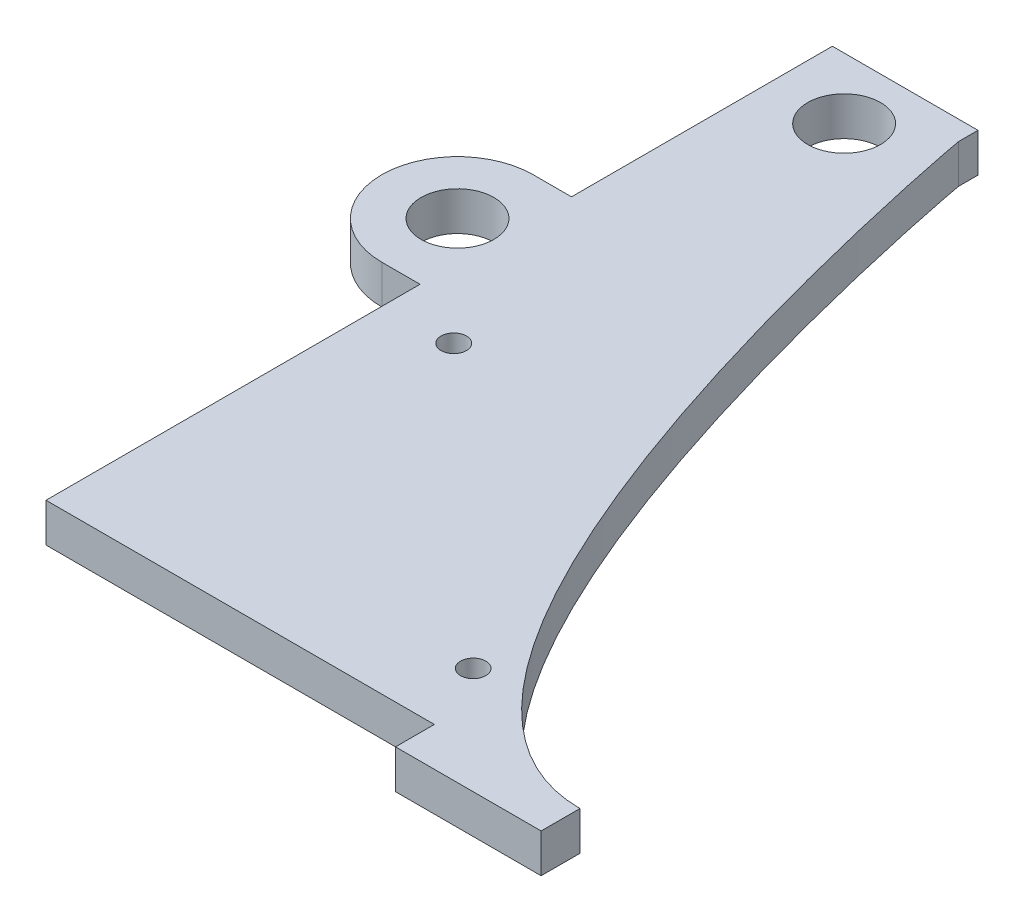
SolidWorks part; units mm, degrees
ref_plane "Front Plane" through (0, 0, 0) normal (0, 0, 1) x (1, 0, 0)
ref_plane "Top Plane" through (0, 0, 0) normal (0, 1, 0) x (1, 0, 0)
ref_plane "Right Plane" through (0, 0, 0) normal (1, 0, 0) x (0, 0, -1)
sketch "Sketch1" plane through (0, 0, 0) normal (0, 1, 0) x (1, 0, 0)
  line L0 (9.525, -53.975) -> (60.325, -53.975) construction
  line L1 (-9.525, -53.975) -> (9.525, -53.975) construction
  line L2 (-9.525, -53.975) -> (-9.525, 53.975) construction
  line L3 (-9.525, 53.975) -> (9.525, 53.975)
  line L4 (9.525, -53.975) -> (9.525, 53.975) construction
  line L5 (-9.525, -53.975) -> (9.525, 53.975) construction
  line L6 (-9.525, 53.975) -> (9.525, -53.975) construction
  line L7 (0, 53.975) -> (0, 45.9867) construction
  line L8 (-9.525, 50.7492) -> (9.525, 50.7492) construction
  line L9 (9.525, 51.435) -> (9.525, 53.975)
  line L10 (60.325, -53.975) -> (60.325, -48.895) construction
  line L11 (60.325, -48.895) -> (-9.525, -48.895) construction
  line L12 (60.325, -53.975) -> (60.325, -48.895) construction
  line L13 (60.325, -48.895) -> (-9.525, -48.895)
  line L14 (-9.525, -48.895) -> (-9.525, 53.975)
  line L15 (31.115, -19.685) -> (31.115, -48.895) construction
  circle A0 centre (0, 45.9867) radius 4.7625
  spline S0 degree 3 poles (9.525, 51.435) (9.525, 51.2145) (27.8191, -48.895) (60.325, -48.895) knots 0 0 0 0 1 1 1 1
  point P4 (0, 0)
  dimension "D5" = 9.525
  dimension "D1" = 107.95
  dimension "D2" = 19.05
  dimension "D3" = 50.8
  dimension "D4" = 2.54
  dimension "D6" = 104.7242
  dimension "D7" = 5.08
  dimension "D8" = 40.64
  dimension "D9" = 29.21
extrude "Boss-Extrude1" add sketch "Sketch1" along normal blind 5.08
sketch "Sketch4" plane through (0, 5.08, 0) normal (0, 1, 0) x (1, 0, 0)
  line L0 (-9.525, 53.975) -> (-9.525, -48.895) construction
  line L1 (60.325, -48.895) -> (41.275, -48.895)
  line L2 (60.325, -48.895) -> (60.325, -53.975)
  line L3 (60.325, -53.975) -> (41.275, -53.975)
  line L4 (41.275, -48.895) -> (41.275, -53.975)
  line L5 (60.325, -48.895) -> (41.275, -53.975) construction
  line L6 (60.325, -53.975) -> (41.275, -48.895) construction
  point P4 (50.8, -51.435)
  dimension "D1" = 50.8
  dimension "D2" = 5.08
extrude "Boss-Extrude2" add sketch "Sketch4" against normal up to surface (5.08 mm away) up to face at (17.145, 0, -2.286)
sketch "Sketch5" plane through (0, 0, 0) normal (0, -1, 0) x (1, 0, 0)
  circle A2 centre (-0.635, 4.445) radius 1.6607
  circle A5 centre (37.465, 40.005) radius 1.651
  point P3 (0, 0)
  point P5 (0, 0)
  point P6 (0, 0)
extrude "Cut-Extrude1" cut sketch "Sketch5" against normal through all both
sketch "Sketch6" plane through (0, 0, 0) normal (0, -1, 0) x (1, 0, 0)
  line L0 (-9.525, -9.9436) -> (-14.5359, -9.9436) construction
  line L1 (-9.525, -53.975) -> (-9.525, 48.895) construction
  line L2 (-14.5359, -0.0376) -> (-9.525, -0.0376)
  line L3 (-14.5359, -19.8496) -> (-9.525, -19.8496)
  line L4 (-9.525, -0.0376) -> (-9.525, -1.3984)
  line L5 (-9.525, -19.8496) -> (-9.525, -18.4887)
  line L6 (41.275, 53.975) -> (60.325, 53.975) construction
  circle A0 centre (-14.5359, -9.9436) radius 4.7625
  arc A1 (-9.525, -18.4887) -> (-9.525, -1.3984) centre (-14.5359, -9.9436) ccw
  arc A2 (-14.5359, -0.0376) -> (-14.5359, -19.8496) centre (-14.5359, -9.9436) ccw
  dimension "D1" = 63.9186
  dimension "D2" = 5.0109
extrude "Boss-Extrude3" add sketch "Sketch6" against normal blind 5.08
sketch "Sketch8" plane through (0, 5.08, 0) normal (0, 1, 0) x (1, 0, 0)
  circle A0 centre (-14.5359, 9.9436) radius 4.7625
